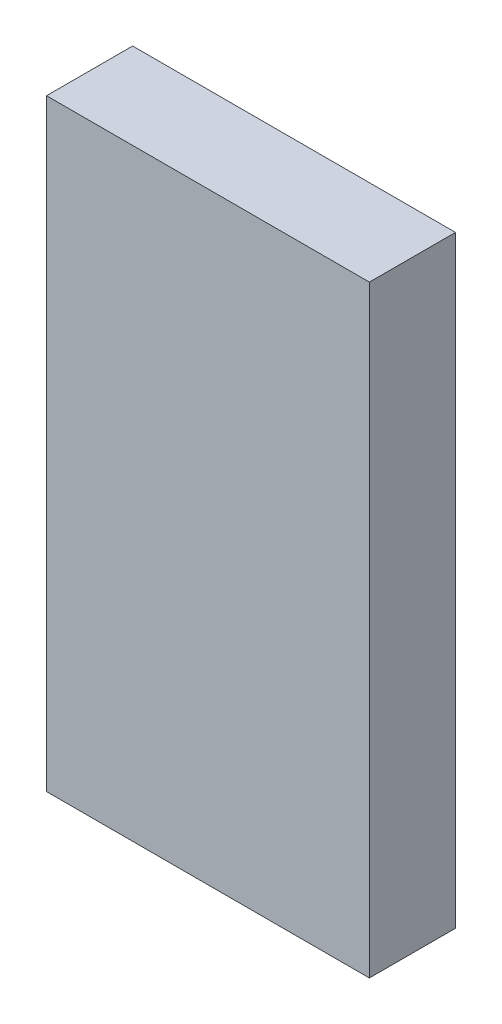
SolidWorks part; units mm, degrees
ref_plane "Front Plane" through (0, 0, 0) normal (0, 0, 1) x (1, 0, 0)
ref_plane "Top Plane" through (0, 0, 0) normal (0, 1, 0) x (1, 0, 0)
ref_plane "Right Plane" through (0, 0, 0) normal (1, 0, 0) x (0, 0, -1)
sketch3d "3DSketch1"
  line L1 (433.0131, 1132.3876, 249.224) -> (283.0131, 1132.3876, 249.224)
  line L2 (433.0131, 1132.3876, 249.224) -> (433.0131, 852.3876, 249.224)
  line L3 (433.0131, 852.3876, 249.224) -> (283.0131, 852.3876, 249.224)
  line L4 (283.0131, 1132.3876, 249.224) -> (283.0131, 852.3876, 249.224)
  line L5 (433.0131, 1132.3876, 249.224) -> (283.0131, 852.3876, 249.224) construction
  line L6 (433.0131, 852.3876, 249.224) -> (283.0131, 1132.3876, 249.224) construction
  point P0 (358.0131, 992.3876, 249.224)
  point P5 (0, 0, 0)
  point P6 (433.0131, 1132.3876, 249.224)
  dimension "D1" = 280
  dimension "D2" = 150
extrude "Boss-Extrude1" add sketch "3DSketch1" along a picked direction on the side of the normal blind 40
